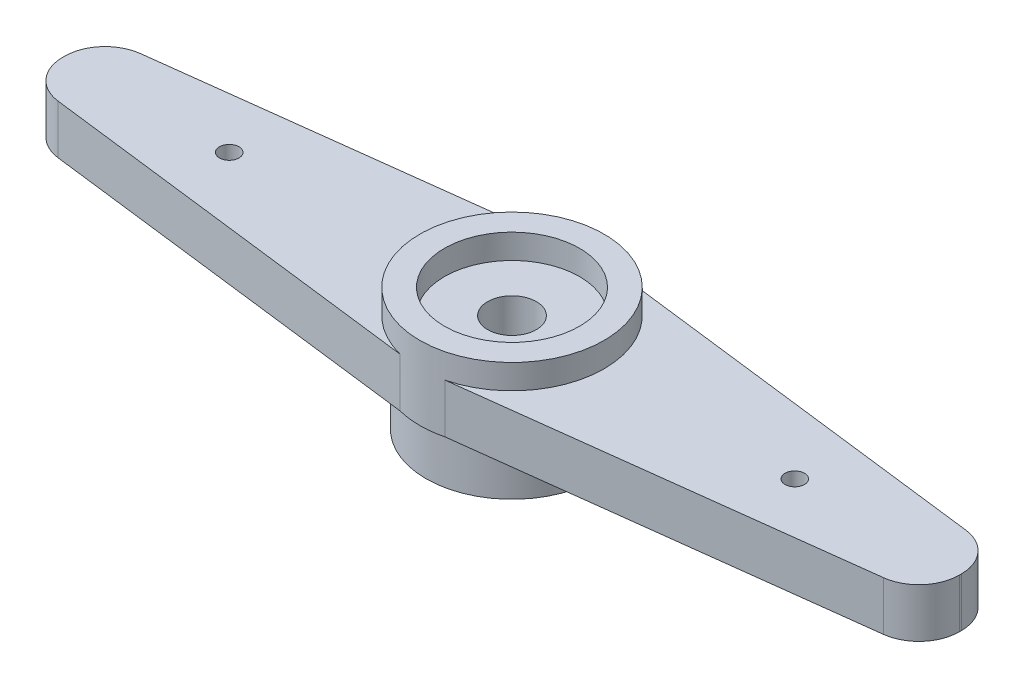
SolidWorks part; units mm, degrees
ref_plane "Front Plane" through (0, 0, 0) normal (0, 0, 1) x (1, 0, 0)
ref_plane "Top Plane" through (0, 0, 0) normal (0, 1, 0) x (1, 0, 0)
ref_plane "Right Plane" through (0, 0, 0) normal (1, 0, 0) x (0, 0, -1)
sketch "Sketch1" plane through (0, 0, 0) normal (0, 1, 0) x (1, 0, 0)
  circle A0 centre (0, 0) radius 3.5
  dimension "D1" = 7
extrude "Boss-Extrude1" add sketch "Sketch1" along normal blind 5
sketch "Sketch2" plane through (0, 0, 0) normal (0, -1, 0) x (1, 0, 0)
  circle A0 centre (0, 0) radius 3
  dimension "D1" = 6
extrude "Cut-Extrude1" cut sketch "Sketch2" against normal blind 4
sketch "Sketch4" plane through (0, 5, 0) normal (0, 1, 0) x (1, 0, 0)
  circle A0 centre (0, 0) radius 3.75
  dimension "D1" = 7.5
extrude "Boss-Extrude2" add sketch "Sketch4" against normal blind 2
sketch "Sketch5" plane through (0, 5, 0) normal (0, 1, 0) x (1, 0, 0)
  circle A0 centre (0, 0) radius 2.75
  dimension "D1" = 5.5
extrude "Cut-Extrude2" cut sketch "Sketch5" against normal blind 1.8
sketch "Sketch6" plane through (0, 3.2, 0) normal (0, 1, 0) x (1, 0, 0)
  circle A0 centre (0, 0) radius 1.1906
  dimension "D1" = 2.3813
extrude "Cut-Extrude3" cut sketch "Sketch6" against normal blind 1.8
sketch "Sketch8" plane through (0, 3, 0) normal (0, -1, 0) x (1, 0, 0)
  line L0 (0, 3.75) -> (-16.8022, 1.6753)
  line L1 (-18.25, 0.0378) -> (-18.25, -0.0378)
  line L2 (-16.8022, -1.6753) -> (0, -3.75)
  circle A0 centre (0, 0) radius 3.75 construction
  arc A1 (-16.8022, -1.6753) -> (-18.25, -0.0378) centre (-16.6, -0.0378) cw
  arc A2 (-16.8022, 1.6753) -> (-18.25, 0.0378) centre (-16.6, 0.0378) ccw
  circle A4 centre (0, 0) radius 3.75
  arc A5 (0, -3.75) -> (0, 3.75) centre (0, 0) ccw
  point P4 (-18.25, 0)
  dimension "D2" = 1.65
  dimension "D1" = 18.25
  dimension "D3" = 0
extrude "Boss-Extrude3" add sketch "Sketch8" against normal blind 2 from offset 1
mirror "Mirror1" about plane through (0, 0, 0) normal (1, 0, 0) of "Boss-Extrude3"
sketch "Sketch9" plane through (0, 4, 0) normal (0, 1, 0) x (1, 0, 0)
  circle A0 centre (0, 0) radius 0.9906
  dimension "D1" = 1.9812
extrude "Cut-Extrude4" cut sketch "Sketch9" against normal through all
sketch "Sketch10" plane through (0, 4, 0) normal (0, 1, 0) x (1, 0, 0)
  circle A0 centre (-11.5094, 0) radius 0.3969
  dimension "D2" = 0.7937
  dimension "D1" = 11.5094
extrude "Cut-Extrude5" cut sketch "Sketch10" against normal through all
mirror "Mirror2" about plane through (0, 0, 0) normal (1, 0, 0) of "Cut-Extrude5"
